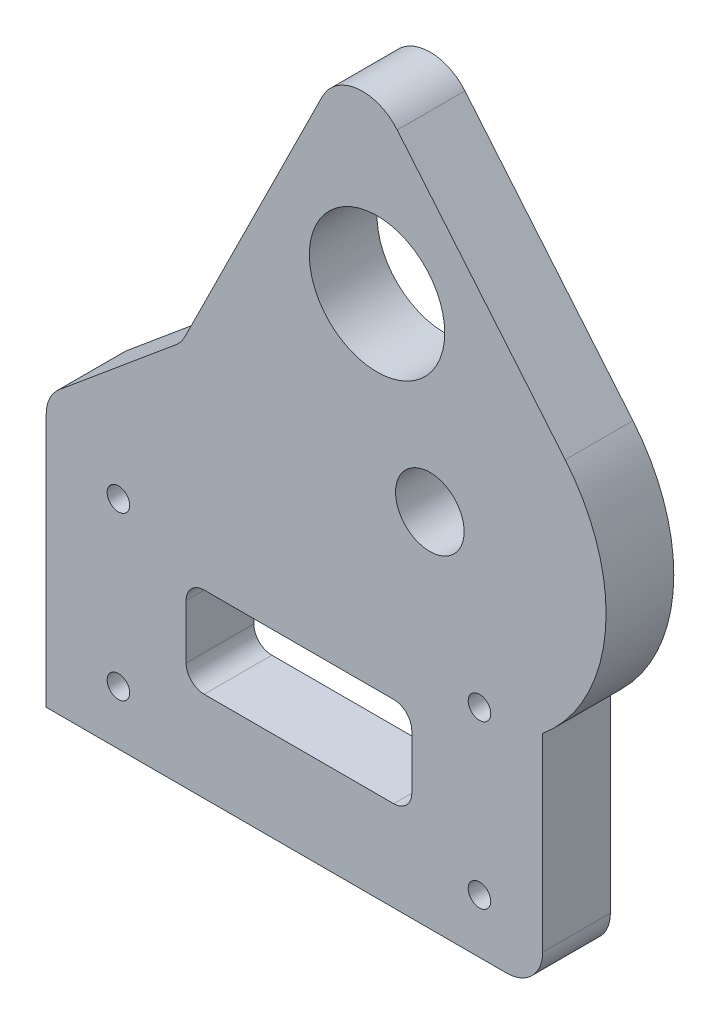
SolidWorks part; units mm, degrees
ref_plane "Front Plane" through (0, 0, 0) normal (0, 0, 1) x (1, 0, 0)
ref_plane "Top Plane" through (0, 0, 0) normal (0, 1, 0) x (1, 0, 0)
ref_plane "Right Plane" through (0, 0, 0) normal (1, 0, 0) x (0, 0, -1)
sketch "Sketch1" plane through (0, 0, 0) normal (0, 0, 1) x (1, 0, 0)
  line L0 (0, 38.1) -> (38.1, 69.85)
  line L1 (0, 0) -> (35.5012, 0)
  line L2 (0, 0) -> (0, 38.1)
  line L5 (19.05, 53.975) -> (38.8216, 93.7987)
  line L6 (49.3874, 95.0401) -> (73.025, 66.675)
  line L8 (38.1, 69.85) -> (69.85, 31.75) construction
  line L9 (35.5012, 0) -> (69.85, 0)
  line L12 (69.85, 0) -> (69.85, 31.75)
  arc A0 (38.1, 69.85) -> (69.85, 31.75) centre (53.975, 50.8) cw
  circle A2 centre (53.975, 50.8) radius 4.826
  circle A3 centre (53.975, 50.8) radius 47.625 construction
  circle A4 centre (44.5092, 90.9749) radius 6.35
  point P0 (0, 0)
  dimension "D6" = 31.75
  dimension "D5" = 0
  dimension "D7" = 9.652
  dimension "D8" = 95.25
  dimension "D9" = 12.7
  dimension "D1" = 38.1
  dimension "D2" = 31.75
  dimension "D3" = 90
  dimension "D4" = 69.85
extrude "Boss-Extrude4" add sketch "Sketch1" along normal blind 9.525 contours L1 L2 | A0 L0 A2 | A4 | A4 L5 L0 | A4 A0 L6 region at (40.084, 33.2843, 0) region at (42.6683, 76.8251, 0) region at (44.5092, 90.9749, 0)
sketch "Sketch2" plane through (0, 0, 9.525) normal (0, 0, 1) x (1, 0, 0)
  line L1 (10.16, 7.62) -> (60.96, 7.62) construction
  line L2 (10.16, 7.62) -> (10.16, 30.48) construction
  line L3 (10.16, 30.48) -> (60.96, 30.48) construction
  line L4 (60.96, 7.62) -> (60.96, 30.48) construction
  line L5 (0, 0) -> (69.85, 0) construction
  line L6 (69.85, 0) -> (69.85, 31.75) construction
  circle A0 centre (10.16, 30.48) radius 1.5875
  circle A1 centre (60.96, 30.48) radius 1.5875
  circle A2 centre (60.96, 7.62) radius 1.5875
  circle A3 centre (10.16, 7.62) radius 1.5875
  dimension "D5" = 3.175
  dimension "D6" = 3.175
  dimension "D7" = 3.175
  dimension "D8" = 3.175
  dimension "D1" = 22.86
  dimension "D2" = 50.8
  dimension "D3" = 8.89
  dimension "D4" = 7.62
extrude "Cut-Extrude2" cut sketch "Sketch2" against normal up to surface (9.525 mm away) contours A0 | A3 | A1 | A2 up to face at (40.8601, 47.6929, 0)
fillet "Fillet1" radius 5.08 1 edges at (69.85, 0, 4.7625)
sketch "Sketch3" plane through (0, 0, 9.525) normal (0, 0, 1) x (1, 0, 0)
  line L0 (19.05, 53.975) -> (38.8216, 93.7987) construction
  line L1 (49.3874, 95.0401) -> (73.025, 66.675) construction
  line L3 (60.96, 30.48) -> (10.16, 30.48) construction
  line L4 (60.96, 30.48) -> (60.96, 7.62) construction
  line L5 (60.96, 7.62) -> (10.16, 7.62) construction
  line L6 (10.16, 30.48) -> (10.16, 7.62) construction
  line L7 (60.96, 30.48) -> (10.16, 7.62) construction
  line L8 (60.96, 7.62) -> (10.16, 30.48) construction
  line L11 (51.435, 12.7) -> (19.685, 12.7)
  line L12 (51.435, 12.7) -> (51.435, 25.4)
  line L13 (51.435, 25.4) -> (19.685, 25.4)
  line L14 (19.685, 12.7) -> (19.685, 25.4)
  line L15 (51.435, 12.7) -> (19.685, 25.4) construction
  line L16 (51.435, 25.4) -> (19.685, 12.7) construction
  circle A0 centre (46.5442, 73.6544) radius 15.875 construction
  circle A1 centre (46.5442, 73.6544) radius 9.525
  circle A2 centre (10.16, 30.48) radius 1.5875 construction
  circle A3 centre (60.96, 7.62) radius 1.5875 construction
  point P7 (35.56, 19.05)
  point P17 (35.56, 19.05)
  dimension "D1" = 31.75
  dimension "D2" = 19.05
  dimension "D3" = 12.7
  dimension "D4" = 31.75
extrude "Cut-Extrude3" cut sketch "Sketch3" against normal up to surface (9.525 mm away) up to face at (11.7475, 7.62, 0)
fillet "Fillet2" radius 2.54 4 edges at (51.435, 12.7, 4.7625) (19.685, 12.7, 4.7625) (19.685, 25.4, 4.7625) (51.435, 25.4, 4.7625)
fillet "Fillet3" radius 5.08 1 edges at (19.05, 53.975, 4.7625)
fillet "Fillet4" radius 5.08 1 edges at (0, 38.1, 4.7625)
